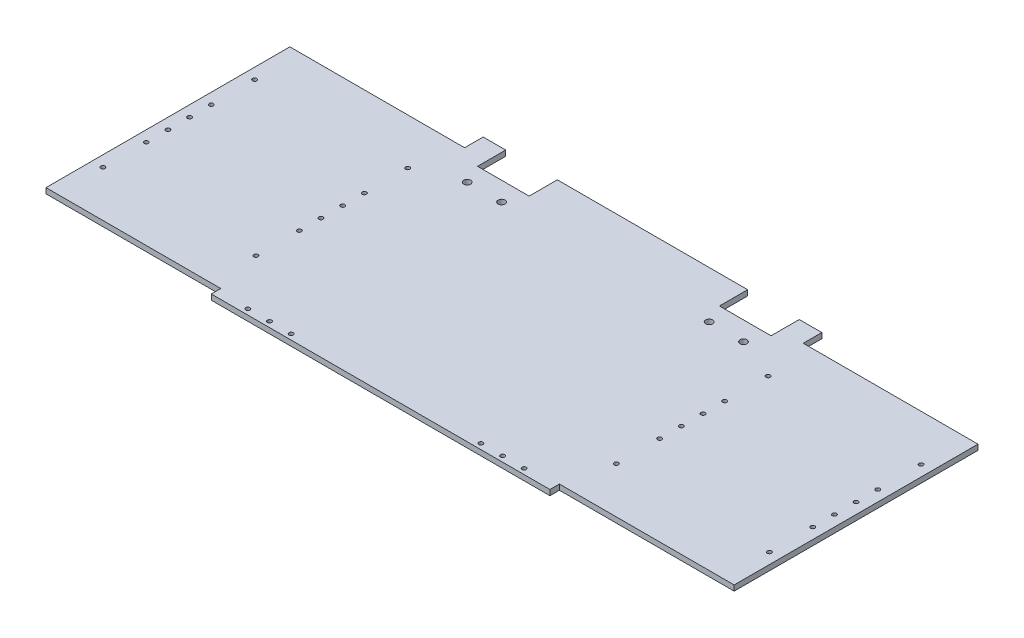
SolidWorks part; units mm, degrees
ref_plane "Front Plane" through (0, 0, 0) normal (0, 0, 1) x (1, 0, 0)
ref_plane "Top Plane" through (0, 0, 0) normal (0, 1, 0) x (1, 0, 0)
ref_plane "Right Plane" through (0, 0, 0) normal (1, 0, 0) x (0, 0, -1)
sketch "Sketch1" plane through (0, 0, 0) normal (0, 1, 0) x (1, 0, 0)
  line L0 (129, 0) -> (129, -7)
  line L1 (0, 0) -> (129, 0)
  line L2 (0, 0) -> (0, 180)
  line L3 (0, 180) -> (129, 180)
  line L4 (508, 0) -> (508, 180)
  line L5 (129, -7) -> (379, -7)
  line L6 (379, -7) -> (379, 0)
  line L7 (0, 90) -> (508, 90) construction
  line L8 (129, 180) -> (129, 193.718)
  line L9 (129, 193.718) -> (145.65, 193.718)
  line L10 (379, 193.718) -> (379, 180)
  line L11 (254, 195.398) -> (254, -38.1) construction
  line L12 (379, 0) -> (508, 0)
  line L13 (379, 180) -> (508, 180)
  line L14 (129, 158.92) -> (379, 158.92) construction
  line L15 (129, -3) -> (254, -3) construction
  line L16 (145.65, 193.718) -> (145.65, 172.89)
  line L17 (145.65, 172.89) -> (183.75, 172.89)
  line L18 (183.75, 172.89) -> (183.75, 193.718)
  line L19 (183.75, 193.718) -> (324.25, 193.718)
  line L20 (324.25, 172.89) -> (362.35, 172.89)
  line L21 (362.35, 193.718) -> (379, 193.718)
  line L23 (362.35, 193.718) -> (362.35, 172.89)
  line L24 (324.25, 172.89) -> (324.25, 193.718)
  circle A0 centre (152, 158.92) radius 2.564
  circle A1 centre (177.4, 158.92) radius 2.564
  circle A4 centre (152, -3) radius 1.55
  circle A5 centre (184, -3) radius 1.55
  circle A8 centre (330.6, 158.92) radius 2.564
  circle A9 centre (356, 158.92) radius 2.564
  circle A10 centre (168, -3) radius 1.55
  circle A11 centre (324, -3) radius 1.55
  circle A12 centre (340, -3) radius 1.55
  circle A13 centre (356, -3) radius 1.55
  circle A14 centre (121, 146) radius 1.55
  circle A15 centre (121, 114) radius 1.55
  circle A16 centre (121, 98) radius 1.55
  circle A17 centre (121, 82) radius 1.55
  circle A18 centre (121, 66) radius 1.55
  circle A19 centre (121, 34) radius 1.55
  circle A20 centre (387, 146) radius 1.55
  circle A21 centre (387, 114) radius 1.55
  circle A22 centre (387, 98) radius 1.55
  circle A23 centre (387, 82) radius 1.55
  circle A24 centre (387, 66) radius 1.55
  circle A25 centre (387, 34) radius 1.55
  circle A26 centre (8, 146) radius 1.55
  circle A27 centre (8, 114) radius 1.55
  circle A28 centre (8, 98) radius 1.55
  circle A29 centre (8, 82) radius 1.55
  circle A30 centre (8, 66) radius 1.55
  circle A31 centre (8, 34) radius 1.55
  circle A32 centre (500, 34) radius 1.55
  circle A33 centre (500, 66) radius 1.55
  circle A34 centre (500, 82) radius 1.55
  circle A35 centre (500, 98) radius 1.55
  circle A36 centre (500, 114) radius 1.55
  circle A37 centre (500, 146) radius 1.55
  point P10 (254, 90)
  dimension "D7" = 3.1
  dimension "D9" = 5.128
  dimension "D16" = 3.1
  dimension "D21" = 3.1
  dimension "D1" = 180
  dimension "D2" = 508
  dimension "D3" = 250
  dimension "D5" = 250
  dimension "D10" = 25.4
  dimension "D11" = 23
  dimension "D12" = 16
  dimension "D13" = 16
  dimension "D14" = 23
  dimension "D15" = 4
  dimension "D4" = 3
  dimension "D17" = 32
  dimension "D19" = 16
  dimension "D20" = 8
  dimension "D18" = 8
  dimension "D22" = 8
  dimension "D23" = 16
  dimension "D24" = 32
  dimension "D25" = 8
  dimension "D8" = 13.718
  dimension "D6" = 21.08
  dimension "D26" = 6.35
  dimension "D27" = 6.35
  dimension "D28" = 13.97
  dimension "D29" = 129
extrude "Boss-Extrude1" add sketch "Sketch1" along normal blind 4
equation "\"cf_tube_outer_diameter\"= 25mm"
equation "\"cf_tube_inner_diameter\" = 21mm"
equation "\"mid_plate_mid_to_top\" = 100mm"
equation "\"mid_plate_mid_to_bottom\" = 30mm"
equation "\"mid_plate_horizontal_spacing\"=250mm"
equation "\"cf_plate_thickness\" =4mm"
equation "\"mid_tube_length\" = 121mm"
equation "\"mid_plate_bottom_width\" = 180mm"
equation "\"D1@Sketch1\"=\"mid_plate_bottom_width\""
equation "\"D1@Boss-Extrude1\"=\"cf_plate_thickness\""
equation "\"D5@Sketch1\"=\"mid_plate_horizontal_spacing\""
equation "\"D3@Sketch1\"=\"mid_plate_horizontal_spacing\""
